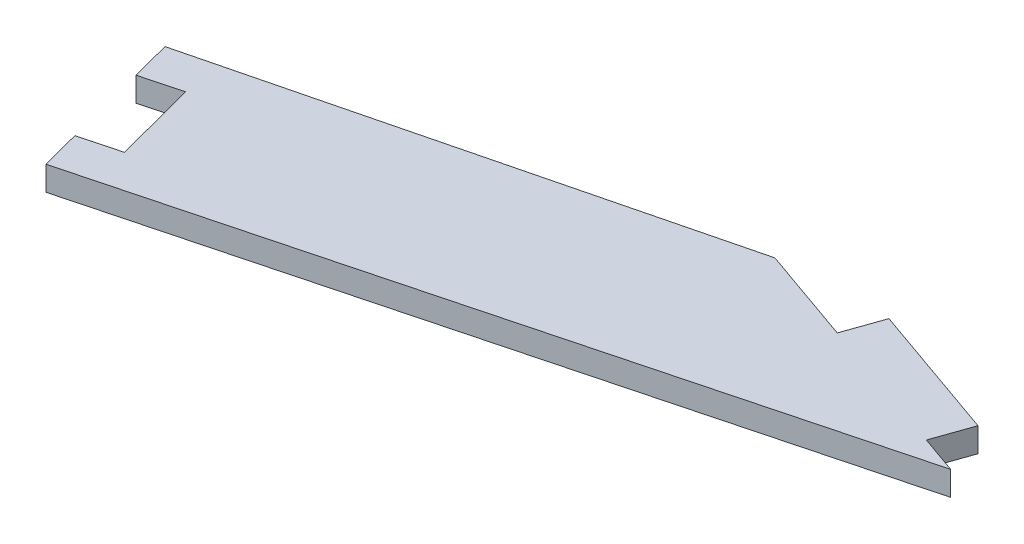
SolidWorks part; units mm, degrees
ref_plane "Front Plane" through (0, 0, 0) normal (0, 0, 1) x (1, 0, 0)
ref_plane "Top Plane" through (0, 0, 0) normal (0, 1, 0) x (1, 0, 0)
ref_plane "Right Plane" through (0, 0, 0) normal (1, 0, 0) x (0, 0, -1)
sketch "Sketch1" plane through (0, 0, 0) normal (0, 1, 0) x (1, 0, 0)
  line L0 (-450, 300) -> (-400, 300)
  line L1 (-400, 300) -> (-200, 250)
  line L2 (-200, 250) -> (200, 250) construction
  line L3 (200, 250) -> (600, 40) construction
  line L4 (600, 40) -> (1200, 40)
  line L5 (-450, -300) -> (-400, -300)
  line L6 (-400, -300) -> (-200, -250)
  line L7 (-200, -250) -> (200, -250) construction
  line L8 (200, -250) -> (600, -40) construction
  line L9 (600, -40) -> (1200, -40)
  line L10 (600, 40) -> (600, -40) construction
  line L11 (200, -250) -> (200, 250) construction
  line L12 (-200, 250) -> (-200, -250) construction
  line L13 (-400, -300) -> (-400, 300) construction
  line L14 (0, 0) -> (200, 0) construction
  line L15 (0, 250) -> (0, 0) construction
  line L16 (1200, 40) -> (1200, -40)
  line L17 (-450, 300) -> (-450, -300)
  line L18 (600, 0) -> (200, 0) construction
  line L19 (-450, 0) -> (-400, 0) construction
  line L20 (-400, 0) -> (-200, 0) construction
  line L21 (-200, 0) -> (0, 0) construction
  line L22 (-200, 250) -> (600, 40)
  line L23 (600, -40) -> (-200, -250)
  dimension "D1" = 600
  dimension "D2" = 200
  dimension "D3" = 50
  dimension "D4" = 400
  dimension "D5" = 500
  dimension "D6" = 80
  dimension "D7" = 600
  dimension "D8" = 400
extrude "Boss-Extrude1" add sketch "Sketch1" along normal blind 15
sketch "Sketch2" plane through (0, 0, 0) normal (0, 0, 1) x (1, 0, 0)
  line L0 (-450, 0) -> (-450, -40)
  line L1 (-450, -40) -> (-400, -40)
  line L2 (-400, -40) -> (-400, 0)
  line L3 (-400, 0) -> (-200, 0) construction
  line L4 (-400, 0) -> (-450, 0)
  line L5 (-440, -15) -> (-440, -40)
  line L6 (-410, -15) -> (-410, -40)
  line L7 (-425, 0) -> (-425, -15) construction
  circle A0 centre (-425, -15) radius 15
  dimension "D1" = 30
  dimension "D2" = 40
extrude "Boss-Extrude2" add sketch "Sketch2" along normal up to surface and the other way up to surface contours L4 L7 A0 L6 L1 L2 | L7 L4 L0 L1 L5 A0 region at (-444.1006, -18.2067, 0) region at (-405.8994, -18.2067, 0) up to face at (-425, 7.5, 300) other way up to face at (-425, 7.5, -300)
sketch "Sketch4" plane through (0, 0, 0) normal (0, 1, 0) x (1, 0, 0)
  line L0 (-450, 230) -> (-400, 230)
  line L1 (-450, 300) -> (-450, -300) construction
  line L2 (-400, 230) -> (-150, 167.5)
  line L3 (-150, 167.5) -> (-150, -167.5)
  line L4 (-150, -167.5) -> (-400, -230)
  line L5 (-400, -230) -> (-450, -230)
  line L6 (-400, 230) -> (-400, -230) construction
  line L7 (-200, 250) -> (-200, -250) construction
  line L9 (-200, 0) -> (-150, 0) construction
  line L10 (-400, -230) -> (-400, -300) construction
  line L11 (-400, -300) -> (-200, -250) construction
  line L12 (-450, 230) -> (-450, -230)
  line L14 (-200, 250) -> (-400, 300) construction
  line L15 (-100, 155) -> (-100, -155)
  line L16 (-100, -155) -> (520, 0)
  line L17 (520, 0) -> (-100, 155)
  line L18 (520, 0) -> (-100, 0) construction
  dimension "D1" = 460
  dimension "D2" = 300
  dimension "D3" = 50
extrude "Cut-Extrude2" cut sketch "Sketch4" against normal through all both and the other way through all
sketch "Sketch5" plane through (0, 0, 0) normal (1, 0, 0) x (0, 0, -1)
  line L0 (-300, 0) -> (-230, 0) construction
  line L1 (-285, 0) -> (-245, 0)
  line L2 (-285, 0) -> (-285, -40)
  line L3 (-285, -40) -> (-245, -40)
  line L4 (-245, 0) -> (-245, -40)
  line L5 (-300, -40) -> (-230, -40) construction
  line L6 (230, 0) -> (300, 0) construction
  line L7 (245, 0) -> (285, 0)
  line L8 (245, 0) -> (245, -40)
  line L9 (245, -40) -> (285, -40)
  line L10 (285, 0) -> (285, -40)
  line L11 (230, -40) -> (300, -40) construction
  line L12 (-300, 0) -> (-300, -40) construction
  line L13 (230, -40) -> (230, 0) construction
  line L14 (300, 0) -> (300, -40) construction
  dimension "D1" = 15
  dimension "D2" = 15
  dimension "D3" = 15
  dimension "D4" = 15
extrude "Cut-Extrude3" cut sketch "Sketch5" against normal through all
sketch "Sketch7" plane through (1200, 0, 0) normal (1, 0, 0) x (0, 0, -1)
  line L1 (-40, 15) -> (-87.5, 50)
  line L2 (-87.5, 50) -> (-87.5, 88.7)
  line L3 (-87.5, 88.7) -> (87.5, 88.7)
  line L4 (87.5, 88.7) -> (87.5, 50)
  line L5 (87.5, 50) -> (40, 15)
  line L7 (-40, 15) -> (40, 15)
  line L8 (-20, 50) -> (-20, 88.7)
  line L9 (87.5, 50) -> (-87.5, 50) construction
  line L10 (0, 88.7) -> (0, 50) construction
  line L11 (-20, 88.7) -> (20, 88.7)
  line L12 (0, 50) -> (0, 0) construction
  line L13 (20, 88.7) -> (20, 50)
  line L14 (-73, 88.7) -> (-63, 88.7)
  line L15 (-73, 88.7) -> (-73, 63.2)
  line L16 (-73, 63.2) -> (-63, 63.2)
  line L17 (-63, 88.7) -> (-63, 63.2)
  line L18 (48.5, 88.7) -> (58.5, 88.7)
  line L19 (48.5, 88.7) -> (48.5, 63.2)
  line L20 (48.5, 63.2) -> (58.5, 63.2)
  line L21 (58.5, 88.7) -> (58.5, 63.2)
  circle A0 centre (0, 50) radius 20
  line M14 (40, 15) -> (-40, 15)
  dimension "D3" = 40
  dimension "D1" = 175
  dimension "D2" = 50
  dimension "D4" = 25.5
  dimension "D5" = 10
  dimension "D6" = 63
  dimension "D7" = 48.5
  dimension "D8" = 38.7
extrude "Boss-Extrude4" add sketch "Sketch7" against normal blind 75 contours L3 L21 L20 L19 L17 L16 L15 L2 L1 L5 L4 M14 region at (1200, 34.0287, 62.6236)
sketch "Sketch8" plane through (0, 0, 0) normal (0, 0, 1) x (1, 0, 0)
  line L0 (1125, 88.7) -> (1200, 88.7) construction
  line L1 (1140, 88.7) -> (1185, 88.7)
  line L2 (1140, 88.7) -> (1140, 15)
  line L3 (1140, 15) -> (1185, 15)
  line L4 (1185, 88.7) -> (1185, 15)
  line L5 (1125, 15) -> (1200, 15) construction
  line L6 (1125, 50) -> (1125, 88.7) construction
  line L7 (1200, 50) -> (1200, 88.7) construction
  line L8 (1155, 88.7) -> (1170, 88.7) construction
  line L9 (1155, 88.7) -> (1170, 88.7)
  line L10 (1155, 88.7) -> (1155, 15)
  line L11 (1155, 15) -> (1170, 15)
  line L12 (1170, 88.7) -> (1170, 15)
  line L15 (1162.5, 50) -> (1162.5, 88.7) construction
  line L16 (1125, 50) -> (1200, 50) construction
  line L17 (1155, 88.7) -> (1170, 88.7) construction
  dimension "D1" = 15
  dimension "D2" = 15
  dimension "D3" = 15
extrude "Cut-Extrude4" cut sketch "Sketch8" against normal through all both and the other way through all contours L10 L1 L2 L3 | L1 L12 L3 L4 region at (1147.5, 51.85, 0) region at (1177.5, 51.85, 0)
fillet "Fillet1" radius 5 53 edges at (1192.5, 50, 87.5) (1162.5, 50, 87.5) (1132.5, 50, 87.5) (1192.5, 50, -87.5) (1162.5, 50, -87.5) (1132.5, 50, -87.5) (1192.5, 88.7, -87.5) (1162.5, 88.7, -87.5) (1132.5, 88.7, -87.5) (1132.5, 88.7, -58.5) (1162.5, 88.7, -58.5) (1192.5, 88.7, -58.5) (1192.5, 88.7, -48.5) (1162.5, 88.7, -48.5) (1132.5, 88.7, -48.5) (1192.5, 88.7, -20) (1162.5, 88.7, -20) (1132.5, 88.7, -20) (1192.5, 88.7, 63) (1162.5, 88.7, 63) (1132.5, 88.7, 63) (1132.5, 88.7, 87.5) (1162.5, 88.7, 87.5) (1192.5, 88.7, 87.5) (1192.5, 88.7, 73) (1162.5, 88.7, 73) (1132.5, 88.7, 73) (1192.5, 88.7, 20) (1162.5, 88.7, 20) (1132.5, 88.7, 20) (600, 7.5, 40) (600, 7.5, -40) (520, 7.5, 0) (-440, -40, -292.5) (-440, -40, -237.5) (-400, -40, -292.5) (-400, -40, -237.5) (-450, -40, -237.5) (-410, -40, -237.5) (-450, -40, -292.5) (-410, -40, -292.5) (-150, 7.5, 167.5) (-100, 7.5, 155) (-150, 7.5, -167.5) (-100, 7.5, -155) (-450, -40, 237.5) (-410, -40, 237.5) (-440, -40, 237.5) (-400, -40, 237.5) (-450, -40, 292.5) (-440, -40, 292.5) (-400, -40, 292.5) (-410, -40, 292.5)
sketch "Sketch9" plane through (0, 0, 0) normal (0, 1, 0) x (1, 0, 0)
  line L35 (-450, -300) -> (-400, -300) construction
  line L36 (-425, -300) -> (-425, -285) construction
  line L37 (-450, 0) -> (0, 0) construction
  line L38 (-437.5, -300) -> (-412.5, -300)
  line L39 (-437.5, -300) -> (-437.5, -285)
  line L56 (1140, -40) -> (1140, -85.466) construction
  line L57 (1200, -40) -> (1185, -40)
  line L58 (1200, -40) -> (1200, -25)
  line L59 (1200, -25) -> (1185, -25)
  line L60 (1185, -40) -> (1185, -25)
  line L61 (1200, 40) -> (1185, 40)
  line L62 (1200, 40) -> (1200, 25)
  line L63 (1200, 25) -> (1185, 25)
  line L64 (1185, 40) -> (1185, 25)
  line L65 (1170, 40) -> (1155, 40)
  line L66 (1170, 40) -> (1170, 25)
  line L67 (1170, 25) -> (1155, 25)
  line L68 (1155, 40) -> (1155, 25)
  line L69 (1140, 40) -> (1125, 40)
  line L70 (1140, 40) -> (1140, 25)
  line L71 (1140, 25) -> (1125, 25)
  line L72 (1125, 40) -> (1125, 25)
  line L73 (1125, -40) -> (1140, -40)
  line L74 (1125, -40) -> (1125, -25)
  line L75 (1125, -25) -> (1140, -25)
  line L76 (1140, -40) -> (1140, -25)
  line L77 (1155, -40) -> (1170, -40)
  line L78 (1155, -40) -> (1155, -25)
  line L79 (1155, -25) -> (1170, -25)
  line L80 (1170, -40) -> (1170, -25)
  line L81 (600.6453, -40) -> (1200, -40) construction
  line L82 (1200, 40) -> (600.6453, 40) construction
  line L83 (1140, 40) -> (1125, 40) construction
  line L84 (1125, 85.466) -> (1125, 40) construction
  line L85 (1140, -25) -> (1155, -25) construction
  line L86 (1170, -25) -> (1185, -25) construction
  line L87 (1185, 25) -> (1170, 25) construction
  line L88 (1155, 25) -> (1140, 25) construction
  line L89 (-437.5, -285) -> (-412.5, -285)
  line L90 (-412.5, -300) -> (-412.5, -285)
  line L92 (-410, -230) -> (-440, -230) construction
  line L93 (-437.5, -230) -> (-412.5, -230)
  line L94 (-437.5, -230) -> (-437.5, -245)
  line L95 (-437.5, -245) -> (-412.5, -245)
  line L96 (-412.5, -230) -> (-412.5, -245)
  line L97 (-425, -245) -> (-400, -245) construction
  line L98 (-425, -285) -> (-425, -245) construction
  line L99 (-425, 285) -> (-425, 245) construction
  line L100 (-425, 300) -> (-425, 285) construction
  line L101 (-450, 300) -> (-400, 300) construction
  line L102 (-412.5, 230) -> (-412.5, 245)
  line L103 (-437.5, 245) -> (-412.5, 245)
  line L104 (-437.5, 230) -> (-437.5, 245)
  line L105 (-437.5, 230) -> (-412.5, 230)
  line L106 (-412.5, 300) -> (-412.5, 285)
  line L107 (-437.5, 285) -> (-412.5, 285)
  line L108 (-437.5, 300) -> (-437.5, 285)
  line L109 (-437.5, 300) -> (-412.5, 300)
  dimension "D1" = 15
  dimension "D2" = 25
  dimension "D3" = 15
extrude "Cut-Extrude5" cut sketch "Sketch9" against normal through all both and the other way through all
sketch "Sketch10" plane through (0, 0, 0) normal (0, 0, 1) x (1, 0, 0)
  line L1 (-450, 15) -> (1200, 15)
  line L2 (-450, 15) -> (-450, 0)
  line L3 (-450, 0) -> (1200, 0)
  line L4 (1200, 15) -> (1200, 0)
  line L5 (-450, 15) -> (-450, -35) construction
  line L6 (-486.0808, 110.0266) -> (1242.84, 110.0266)
  line L7 (-486.0808, 110.0266) -> (-486.0808, -68.8272)
  line L8 (-486.0808, -68.8272) -> (1242.84, -68.8272)
  line L9 (1242.84, 110.0266) -> (1242.84, -68.8272)
  dimension "D1" = 15
extrude "Cut-Extrude6" cut sketch "Sketch10" against normal through all both and the other way through all
sketch "Sketch11" plane through (0, 0, 0) normal (0, 1, 0) x (1, 0, 0)
  line L0 (-450, -315.625) -> (323.7848, -112.5065)
  line L1 (-200, -250) -> (599.3758, -40.1638) construction
  line L2 (-450, -315.625) -> (-450, -242.5)
  line L3 (-450, -230) -> (-450, -300) construction
  line L4 (-450, -242.5) -> (308.1542, -52.9615)
  line L5 (308.1542, -52.9615) -> (323.7848, -112.5065)
  line L6 (-400, -230) -> (-153.7873, -168.4468) construction
  line L7 (-450, -242.5) -> (-450, -230)
  line L8 (-450, -230) -> (-400, -230)
  line L9 (-150, -167.5) -> (-150, -182.5)
  line L10 (-150, -182.5) -> (-135, -182.5)
  line L11 (-135, -182.5) -> (-135, -163.75)
  line L12 (-100, -155) -> (-100, -182.5)
  line L13 (-100, -182.5) -> (-115, -182.5)
  line L14 (-115, -182.5) -> (-115, -158.75)
  line L15 (-100, 148.5961) -> (-100, -148.5961) construction
  line L16 (-150, -163.5961) -> (-150, 163.5961) construction
  line L17 (309.2763, -116.315) -> (305.4678, -101.8065)
  line L18 (-601.3695, -564.0724) -> (1251.3111, -564.0724)
  line L19 (-601.3695, -564.0724) -> (-601.3695, 511.8547)
  line L20 (-601.3695, 511.8547) -> (1251.3111, 511.8547)
  line L21 (1251.3111, -564.0724) -> (1251.3111, 511.8547)
  line L22 (305.4678, -101.8065) -> (319.9763, -97.998)
  line L23 (293.6011, -56.5997) -> (297.4095, -71.1082)
  line L24 (297.4095, -71.1082) -> (311.918, -67.2997)
  line L25 (305.4678, -101.8065) -> (297.4095, -71.1082) construction
  line L26 (323.7848, -112.5065) -> (600.6453, -40)
  line L27 (600.6453, -40) -> (500.5971, -4.8507)
  line L28 (500.5971, -4.8507) -> (308.1542, -52.9615)
  line L29 (574.7182, -46.79) -> (474.1575, -11.4606)
  line L30 (560.5662, -41.8181) -> (565.5382, -27.666)
  line L31 (509.7772, -23.9747) -> (514.7492, -9.8227)
  dimension "D1" = 800
  dimension "D2" = 15
  dimension "D3" = 15
  dimension "D4" = 15
  dimension "D5" = 15
  dimension "D6" = 15
  dimension "D7" = 15
  dimension "D8" = 15
extrude "Cut-Extrude7" cut sketch "Sketch11" along normal through all contours L18 L21 L20 L19 L28 L27 L26 L0 L2 L7 L8 L4 | L8 L7 L4 | L17 L25 L23 L4 L12 L13 L14 L11 L10 L9 L2 L0 | L10 L11 L4 L9 | L14 L13 L12 L4 | L30 L29 L26 L27 | L29 L31 L27 L28 | L25 L22 L5 L24 region at (-82.3798, 0, 185.2581) region at (-433.3333, 0, 234.1667) region at (308.6929, 0, 84.5531) region at (576.4624, 0, 38.3261) region at (-142.2222, 0, 174.0278) region at (498.6912, 0, 13.2734) region at (-107.3171, 0, 169.6646) region at (335.1612, 0, 21.5895)
sketch "Sketch12" plane through (0, 0, 0) normal (0, 0, 1) x (1, 0, 0)
  line L0 (293.6011, 15) -> (293.6011, 0) construction
  line L1 (574.4681, 15) -> (293.6011, 15)
  line L2 (574.4681, 15) -> (574.4681, 9)
  line L3 (574.4681, 9) -> (293.6011, 9)
  line L4 (293.6011, 15) -> (293.6011, 9)
  line L5 (309.2763, 0) -> (574.4681, 0) construction
  dimension "D1" = 9
extrude "Cut-Extrude8" cut sketch "Sketch12" against normal through all both and the other way through all
